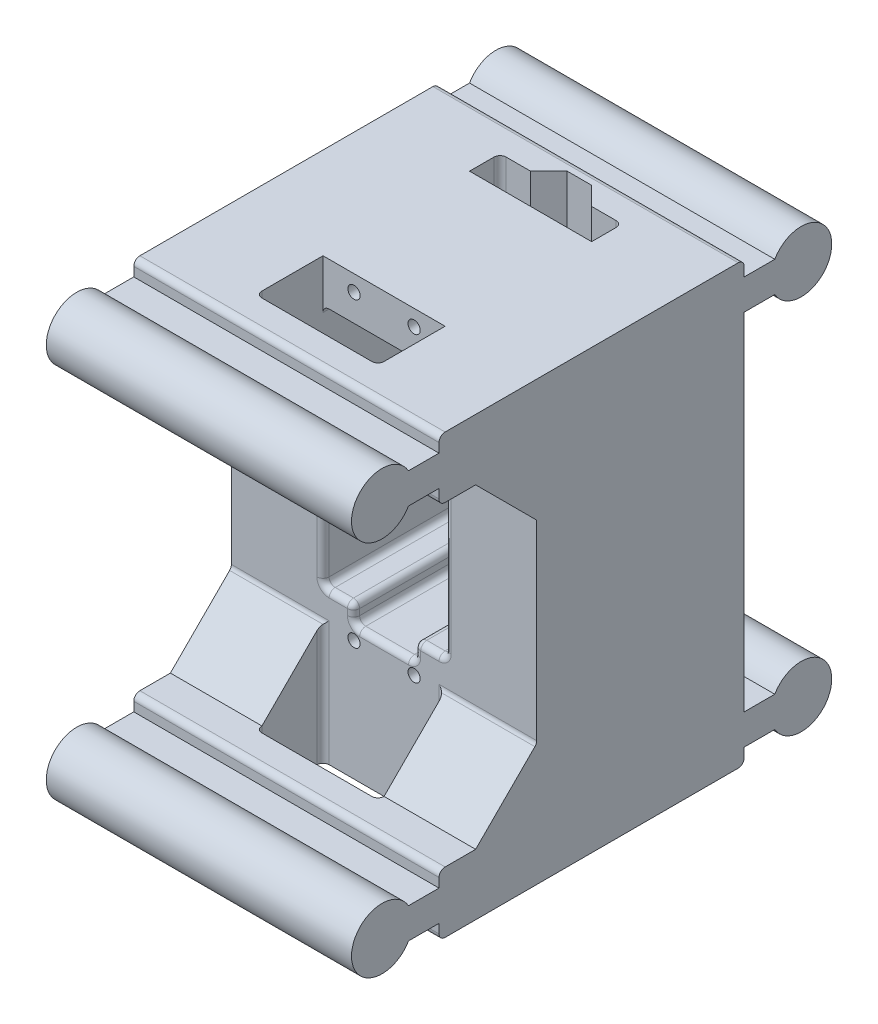
SolidWorks part; units mm, degrees
ref_plane "Plano frontal" through (0, 0, 0) normal (0, 0, 1) x (1, 0, 0)
ref_plane "Plano superior" through (0, 0, 0) normal (0, 1, 0) x (1, 0, 0)
ref_plane "Plano direito" through (0, 0, 0) normal (1, 0, 0) x (0, 0, -1)
sketch "Esboço2" plane through (0, 0, 0) normal (0, 0, 1) x (1, 0, 0)
  line L0 (0, 0) -> (0, 24.1482) construction
  line L1 (-10, 0) -> (10, 0) construction
  line L2 (10, 0) -> (10, -40)
  line L3 (10, 0) -> (-10, 0)
  line L4 (25, 0) -> (25, 7.05)
  line L5 (25, 7.05) -> (-25, 7.05)
  line L6 (0, 0) -> (0, 7.05) construction
  line L8 (25, -40) -> (25, 0)
  line L9 (-25, -40) -> (-25, 0)
  line L11 (-25, 0) -> (-25, 7.05)
  line L12 (-10, 0) -> (-10, -40)
  line L14 (-10, -40) -> (10, -40)
  line L15 (-25, -40) -> (-25, -64.65)
  line L16 (-25, -64.65) -> (25, -64.65)
  line L17 (25, -40) -> (25, -64.65)
  dimension "D1" = 20
  dimension "D2" = 7.05
  dimension "D3" = 40
  dimension "D4" = 15
  dimension "D5" = 24.65
  dimension "D6" = 50
extrude "Ressalto-extrusão2" add sketch "Esboço2" against normal blind 29
sketch "Esboço3" plane through (0, 0, 0) normal (0, 0, 1) x (1, 0, 0)
  line L0 (25, -64.65) -> (25, 7.05) construction
  line L1 (10, 7.05) -> (25, 7.05)
  line L2 (10, 7.05) -> (10, -2.95)
  line L3 (10, -2.95) -> (25, -2.95)
  line L4 (25, 7.05) -> (25, -2.95)
  line L5 (0, -15.95) -> (0, 15.95) construction
  line L6 (-25, 7.05) -> (-25, -2.95)
  line L7 (-10, -2.95) -> (-25, -2.95)
  line L8 (-10, 7.05) -> (-10, -2.95)
  line L9 (-10, 7.05) -> (-25, 7.05)
  line L11 (25, 7.05) -> (-25, 7.05) construction
  point P13 (0, 0)
  dimension "D1" = 10
extrude "Ressalto-extrusão3" add sketch "Esboço3" along normal blind 16
sketch "Esboço4" plane through (10, 0, 0) normal (-1, 0, 0) x (0, 0, 1)
  line L0 (16, -2.95) -> (0, -2.95) construction
  line L1 (16, 7.05) -> (11, 7.05)
  line L2 (16, 7.05) -> (16, -2.95)
  line L3 (16, -2.95) -> (11, -2.95)
  line L4 (11, 7.05) -> (11, -2.95)
  dimension "D1" = 5
extrude "Ressalto-extrusão4" add sketch "Esboço4" along normal up to surface (20 mm away) up to face at (-10, -8.975, -3.25)
sketch "Esboço5" plane through (0, 0, -29) normal (0, 0, -1) x (-1, 0, 0)
  line L1 (25, 7.05) -> (-25, 7.05)
  line L2 (25, 7.05) -> (25, -64.65)
  line L3 (25, -64.65) -> (-25, -64.65)
  line L4 (-25, 7.05) -> (-25, -64.65)
  point P8 (0, 0)
extrude "Ressalto-extrusão5" add sketch "Esboço5" along normal blind 5
sketch "Esboço6" plane through (-25, 0, 0) normal (-1, 0, 0) x (0, 0, 1)
  line L0 (16, 2.05) -> (25.3301, 2.05) construction
  line L1 (16, 7.05) -> (16, -2.95) construction
  line L2 (16, 4.55) -> (21, 4.55)
  line L3 (16, -0.45) -> (21, -0.45)
  line L4 (16, 7.05) -> (-34, 7.05) construction
  line L5 (16, -2.95) -> (0, -2.95) construction
  line L6 (16, 4.55) -> (16, -0.45)
  line L7 (16, 2.05) -> (-34, 2.05) construction
  line L8 (-34, -64.65) -> (-34, 7.05) construction
  line L9 (-9, 2.05) -> (-9, 7.05) construction
  line L10 (-34, 7.05) -> (16, 7.05) construction
  line L11 (-34, 2.05) -> (-43.3301, 2.05) construction
  line L12 (-34, 4.55) -> (-34, -0.45)
  line L13 (-34, -0.45) -> (-39, -0.45)
  line L14 (-34, 4.55) -> (-39, 4.55)
  arc A0 (21, -0.45) -> (21, 4.55) centre (25.3301, 2.05) ccw
  arc A1 (-39, -0.45) -> (-39, 4.55) centre (-43.3301, 2.05) cw
  dimension "D3" = 10
  dimension "D1" = 2.5
  dimension "D2" = 2.5
  dimension "D4" = 5
extrude "Ressalto-extrusão6" add sketch "Esboço6" against normal up to surface (50 mm away) up to face at (25, -20.1833, -6)
ref_plane "Plano1" through (0, -28.8, 0) normal (0, -1, 0) x (-1, 0, 0)
mirror "Espelhar2" about plane through (0, -28.8, 0) normal (0, -1, 0) of "Ressalto-extrusão4", "Ressalto-extrusão3", "Ressalto-extrusão6"
sketch "Esboço9" plane through (0, 0, 0) normal (0, 0, 1) x (1, 0, 0)
  line L0 (-10, -40) -> (10, -40) construction
  line L1 (-5, -37) -> (5, -37)
  line L2 (-5, -37) -> (-5, -43)
  line L3 (-5, -43) -> (5, -43)
  line L4 (5, -37) -> (5, -43)
  line L5 (-5, -37) -> (5, -43) construction
  line L6 (-5, -43) -> (5, -37) construction
  point P0 (0, -40)
  dimension "D1" = 10
  dimension "D2" = 6
extrude "Corte-extrusão1" cut sketch "Esboço9" against normal up to surface (29 mm away) up to face at (0, -20, -29)
sketch "Esboço10" plane through (0, 0, 0) normal (0, -1, 0) x (1, 0, 0)
  line L0 (10, -29) -> (10, 0) construction
  line L1 (-10, -29) -> (10, -29)
  line L2 (-10, -29) -> (-10, -24)
  line L3 (-10, -24) -> (10, -24)
  line L4 (10, -29) -> (10, -24)
  dimension "D1" = 5
extrude "Corte-extrusão2" cut sketch "Esboço10" against normal up to surface (7.05 mm away) up to face at (0, 7.05, 5.5)
sketch "Esboço11" plane through (0, 0, -29) normal (0, 0, 1) x (1, 0, 0)
  line L0 (0, 7.05) -> (0, -43) construction
  line L1 (-10, 7.05) -> (10, 7.05) construction
  line L2 (5, -43) -> (-5, -43) construction
  line L3 (0, -17.975) -> (10, -17.975) construction
  line L4 (10, -40) -> (10, 7.05) construction
  line L6 (-5, 7.05) -> (5, 7.05)
  line L7 (-5, 7.05) -> (-5, -43)
  line L8 (-5, -43) -> (5, -43)
  line L9 (5, 7.05) -> (5, -43)
  line L10 (-5, 7.05) -> (5, -43) construction
  line L11 (-5, -43) -> (5, 7.05) construction
extrude "Corte-extrusão3" cut sketch "Esboço11" against normal blind 3
chamfer "Chanfro4" distance 3 angle 45 2 edges at (-5, -17.975, -32) (5, -17.975, -32)
sketch "Esboço12" plane through (0, 0, 0) normal (0, 0, 1) x (1, 0, 0)
  line L0 (0, 7.05) -> (0, -54.65) construction
  line L1 (10, 7.05) -> (-10, 7.05) construction
  line L2 (25, -54.65) -> (-25, -54.65) construction
  line L4 (-4.925, 4.42) -> (4.925, 4.42) construction
  line L5 (-4.925, 4.42) -> (-4.925, -45) construction
  line L6 (-4.925, -45) -> (4.925, -45) construction
  line L7 (4.925, 4.42) -> (4.925, -45) construction
  circle A0 centre (-4.925, 4.42) radius 1
  circle A1 centre (4.925, 4.42) radius 1
  circle A2 centre (4.925, -45) radius 1
  circle A3 centre (-4.925, -45) radius 1
  point P10 (0, 4.42)
  dimension "D1" = 2
  dimension "D2" = 9.85
  dimension "D3" = 2.63
  dimension "D4" = 49.42
extrude "Corte-extrusão4" cut sketch "Esboço12" against normal blind 10
chamfer "Chanfro5" distance 10 angle 45 4 edges at (-17.5, -54.65, 0) (17.5, -54.65, 0) (17.5, -2.95, 0) (-17.5, -2.95, 0)
fillet "Filete2" radius 1 31 edges at (-10, 0, -12) (10, 0, -12) (-10, -40, -14.5) (10, -40, -14.5) (5, -40, -14.5) (5, -43, -14.5) (-5, -43, -14.5) (-5, -40, -14.5) (-5, -41.5, 0) (5, -41.5, 0) (7.5, -40, 0) (-7.5, -40, 0) (10, -59.65, 11) (-10, -59.65, 11) (10, -54.65, 0) (-10, -54.65, 0) (10, 2.05, 11) (-10, 2.05, 11) (0, -43, 0) (10, -26.475, 0) (-10, -26.475, 0) (10, -16.475, -29) (-10, -16.475, -29) (0, -64.65, -34) (0, 7.05, -34) (0, -64.65, 16) (0, -54.65, 16) (0, -2.95, 16) (0, 7.05, 16) (-17.5, -44.65, 0) (17.5, -44.65, 0)
sketch "Esboço19" plane through (-25, 0, 0) normal (-1, 0, 0) x (0, 0, 1)
  line L0 (-33, 7.05) -> (15, 7.05) construction
  line L1 (-34, -57.15) -> (-34, -0.45) construction
  circle A0 centre (-26, 2.05) radius 2.05
  circle A1 centre (-6, 2.05) radius 2.05
  point P4 (0, 0)
  dimension "D1" = 4.1
  dimension "D2" = 5
  dimension "D3" = 8
  dimension "D4" = 20
extrude "Corte-extrusão7" cut sketch "Esboço19" against normal blind 10
